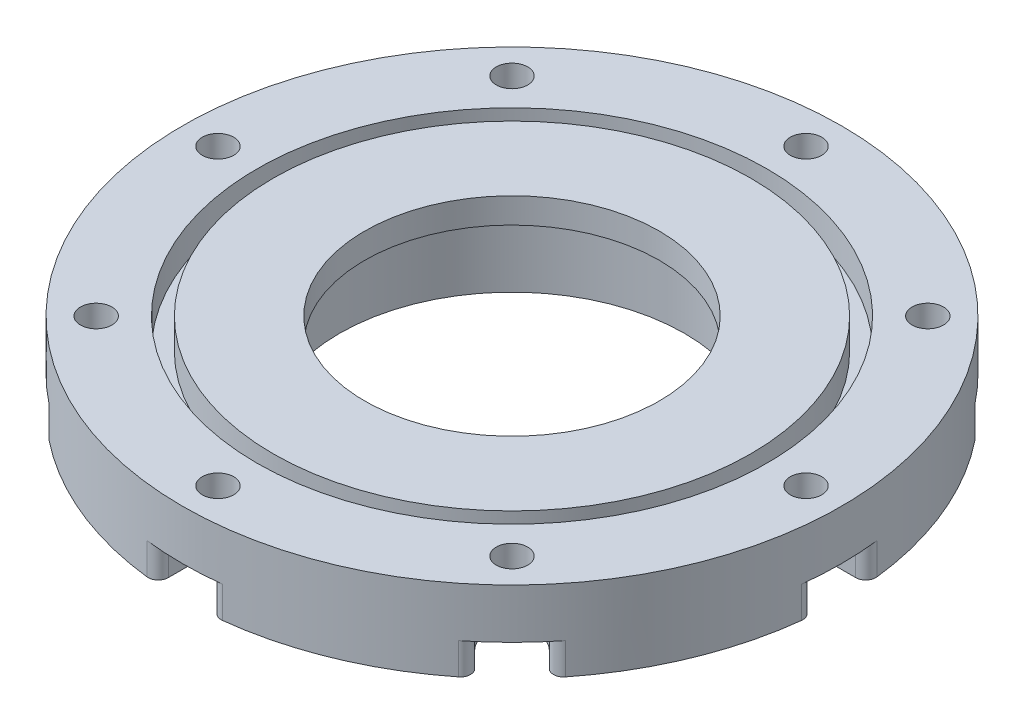
SolidWorks part; units mm, degrees
material "PVC rigide"
ref_plane "Plan de face" through (0, 0, 0) normal (0, 0, 1) x (1, 0, 0)
ref_plane "Plan de dessus" through (0, 0, 0) normal (0, 1, 0) x (1, 0, 0)
ref_plane "Plan de droite" through (0, 0, 0) normal (1, 0, 0) x (0, 0, -1)
sketch "Esquisse1" plane through (0, 0, 0) normal (0, 0, 1) x (1, 0, 0)
  line L0 (0, 0) -> (0, 40.6897) construction
  line L1 (-34.05, 0) -> (-34.05, 15)
  line L2 (-34.05, 15) -> (-29.05, 15)
  line L3 (-29.05, 15) -> (-29.05, 20)
  line L4 (-29.05, 20) -> (-47.1, 20)
  line L5 (-47.1, 20) -> (-47.1, 14)
  line L6 (-47.1, 14) -> (-50.3, 14)
  line L7 (-50.3, 14) -> (-50.3, 20)
  line L8 (-50.3, 20) -> (-65, 20)
  line L9 (-65, 20) -> (-65, 0)
  line L10 (-65, 0) -> (-34.05, 0)
  line L11 (-57.65, 20) -> (-57.65, 0) construction
  dimension "D1" = 20
  dimension "D2" = 5
  dimension "D3" = 68.1
  dimension "D4" = 5
  dimension "D5" = 94.2
  dimension "D6" = 100.6
  dimension "D7" = 130
  dimension "D8" = 14.7
  dimension "D9" = 6
revolve "Révolution1" add sketch "Esquisse1" angle 360 about L0
sketch "Esquisse2" plane through (0, 0, 0) normal (0, -1, 0) x (1, 0, 0)
  line L0 (0, 0) -> (0, 65) construction
  circle A0 centre (0, 0) radius 65 construction
  circle A1 centre (0, 58) radius 3.1
  circle A2 centre (41.0122, 41.0122) radius 3.1
  circle A3 centre (58, 0) radius 3.1
  circle A4 centre (41.0122, -41.0122) radius 3.1
  circle A5 centre (0, -58) radius 3.1
  circle A6 centre (-41.0122, -41.0122) radius 3.1
  circle A7 centre (-58, 0) radius 3.1
  circle A8 centre (-41.0122, 41.0122) radius 3.1
  dimension "D2" = 6.2
  dimension "D1" = 58
  dimension "D3" = 8
extrude "Enlèv. mat.-Extru.1" cut sketch "Esquisse2" against normal through all
sketch "Esquisse4" plane through (0, 0, 0) normal (0, -1, 0) x (1, 0, 0)
  circle A0 centre (0, 0) radius 42.05
  circle A1 centre (0, 0) radius 34.05 construction
  dimension "D1" = 8
extrude "Enlèv. mat.-Extru.3" cut sketch "Esquisse4" against normal blind 4 flip side to cut
sketch "Esquisse3" plane through (0, 4, 0) normal (0, -1, 0) x (1, 0, 0)
  circle A0 centre (0, 58) radius 5.1
  circle A1 centre (41.0122, 41.0122) radius 5.1
  circle A2 centre (58, 0) radius 5.1
  circle A3 centre (41.0122, -41.0122) radius 5.1
  circle A4 centre (0, -58) radius 5.1
  circle A5 centre (-41.0122, -41.0122) radius 5.1
  circle A6 centre (-58, 0) radius 5.1
  circle A7 centre (-41.0122, 41.0122) radius 5.1
  dimension "D1" = 10.2
  dimension "D2" = 8
extrude "Enlèv. mat.-Extru.2" cut sketch "Esquisse3" against normal blind 6.2
sketch "Esquisse5" plane through (0, 4, 0) normal (0, -1, 0) x (1, 0, 0)
  line L0 (0, -58) -> (0, -69.173) construction
  line L1 (5.2, -58) -> (5.2, -69.173)
  line L2 (-5.2, -58) -> (-5.2, -69.173)
  line L3 (-41.0122, -41.0122) -> (-48.9127, -48.9127) construction
  line L4 (-37.3352, -44.6891) -> (-45.2357, -52.5897)
  line L5 (-44.6891, -37.3352) -> (-52.5897, -45.2357)
  line L6 (-58, 0) -> (-69.173, 0) construction
  line L7 (-58, -5.2) -> (-69.173, -5.2)
  line L8 (-58, 5.2) -> (-69.173, 5.2)
  line L9 (-41.0122, 41.0122) -> (-48.9127, 48.9127) construction
  line L10 (-44.6891, 37.3352) -> (-52.5897, 45.2357)
  line L11 (-37.3352, 44.6891) -> (-45.2357, 52.5897)
  line L12 (0, 58) -> (0, 69.173) construction
  line L13 (-5.2, 58) -> (-5.2, 69.173)
  line L14 (5.2, 58) -> (5.2, 69.173)
  line L15 (41.0122, 41.0122) -> (48.9127, 48.9127) construction
  line L16 (37.3352, 44.6891) -> (45.2357, 52.5897)
  line L17 (44.6891, 37.3352) -> (52.5897, 45.2357)
  line L18 (58, 0) -> (69.173, 0) construction
  line L19 (58, 5.2) -> (69.173, 5.2)
  line L20 (58, -5.2) -> (69.173, -5.2)
  line L21 (41.0122, -41.0122) -> (48.9127, -48.9127) construction
  line L22 (44.6891, -37.3352) -> (52.5897, -45.2357)
  line L23 (37.3352, -44.6891) -> (45.2357, -52.5897)
  arc A0 (5.2, -58) -> (-5.2, -58) centre (0, -58) ccw
  arc A1 (-5.2, -69.173) -> (5.2, -69.173) centre (0, -69.173) ccw
  arc A2 (-37.3352, -44.6891) -> (-44.6891, -37.3352) centre (-41.0122, -41.0122) ccw
  arc A3 (-52.5897, -45.2357) -> (-45.2357, -52.5897) centre (-48.9127, -48.9127) ccw
  arc A4 (-58, -5.2) -> (-58, 5.2) centre (-58, 0) ccw
  arc A5 (-69.173, 5.2) -> (-69.173, -5.2) centre (-69.173, 0) ccw
  arc A6 (-44.6891, 37.3352) -> (-37.3352, 44.6891) centre (-41.0122, 41.0122) ccw
  arc A7 (-45.2357, 52.5897) -> (-52.5897, 45.2357) centre (-48.9127, 48.9127) ccw
  arc A8 (-5.2, 58) -> (5.2, 58) centre (0, 58) ccw
  arc A9 (5.2, 69.173) -> (-5.2, 69.173) centre (0, 69.173) ccw
  arc A10 (37.3352, 44.6891) -> (44.6891, 37.3352) centre (41.0122, 41.0122) ccw
  arc A11 (52.5897, 45.2357) -> (45.2357, 52.5897) centre (48.9127, 48.9127) ccw
  arc A12 (58, 5.2) -> (58, -5.2) centre (58, 0) ccw
  arc A13 (69.173, -5.2) -> (69.173, 5.2) centre (69.173, 0) ccw
  arc A14 (44.6891, -37.3352) -> (37.3352, -44.6891) centre (41.0122, -41.0122) ccw
  arc A15 (45.2357, -52.5897) -> (52.5897, -45.2357) centre (48.9127, -48.9127) ccw
  point P4 (0, -63.5865)
  point P13 (-44.9624, -44.9624)
  point P20 (-63.5865, 0)
  point P27 (-44.9624, 44.9624)
  point P34 (0, 63.5865)
  point P41 (44.9624, 44.9624)
  point P48 (63.5865, 0)
  point P55 (44.9624, -44.9624)
  dimension "D1" = 5.2
  dimension "D2" = 8
extrude "Enlèv. mat.-Extru.4" cut sketch "Esquisse5" against normal up to surface (6.2 mm away) up to face at (41.0122, 10.2, -46.1122)
fillet "Congé2" radius 2 16 edges at (42.1377, 7.1, -49.4916) (5.2, 7.1, -64.7917) (-5.2, 7.1, -64.7917) (-42.1377, 7.1, -49.4916) (-49.4916, 7.1, -42.1377) (-64.7917, 7.1, -5.2) (-64.7917, 7.1, 5.2) (-49.4916, 7.1, 42.1377) (-5.2, 7.1, 64.7917) (5.2, 7.1, 64.7917) (42.1377, 7.1, 49.4916) (49.4916, 7.1, 42.1377) (64.7917, 7.1, 5.2) (64.7917, 7.1, -5.2) (49.4916, 7.1, -42.1377) (-42.1377, 7.1, 49.4916)
